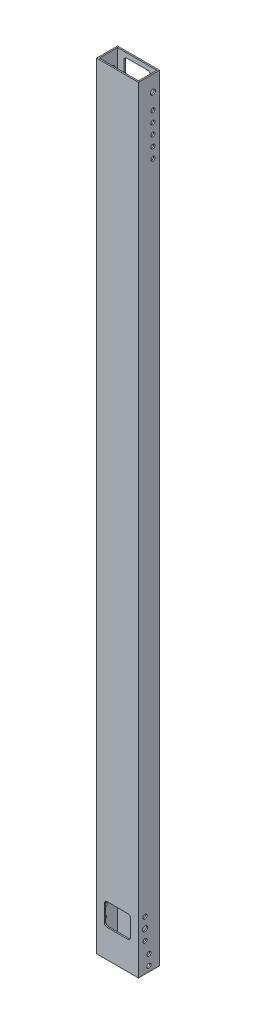
SolidWorks part; units mm, degrees
material "6061-T6 (SS)"
ref_plane "Front Plane" through (0, 0, 0) normal (0, 0, 1) x (1, 0, 0)
ref_plane "Top Plane" through (0, 0, 0) normal (0, 1, 0) x (1, 0, 0)
ref_plane "Right Plane" through (0, 0, 0) normal (1, 0, 0) x (0, 0, -1)
sketch "Sketch1" plane through (0, 0, 0) normal (0, 0, 1) x (1, 0, 0)
  line L1 (-25.4, -469.9) -> (25.4, -469.9)
  line L2 (-25.4, -469.9) -> (-25.4, 469.9)
  line L3 (-25.4, 469.9) -> (25.4, 469.9)
  line L4 (25.4, -469.9) -> (25.4, 469.9)
  line L5 (-25.4, -469.9) -> (25.4, 469.9) construction
  line L6 (-25.4, 469.9) -> (25.4, -469.9) construction
  point P0 (0, 0)
  dimension "D1" = 50.8
  dimension "D2" = 939.8
extrude "Boss-Extrude1" add sketch "Sketch1" along normal mid plane 25.4
shell "Shell1" thickness 1.5875 removed face at (0, -469.9, 0) removed face at (0, 469.9, 0)
sketch "Sketch3" plane through (0, 0, 0) normal (1, 0, 0) x (0, 0, -1)
  line L0 (-12.7, -469.9) -> (12.7, -469.9) construction
  circle A0 centre (0, -463.55) radius 2.4892
  circle A1 centre (0, -450.85) radius 2.4892
  point P6 (0, -469.9)
  dimension "D1" = 4.9784
  dimension "D2" = 6.35
  dimension "D3" = 12.7
extrude "Cut-Extrude1" cut sketch "Sketch3" against normal through all both and the other way through all
sketch "Sketch4" plane through (0, 0, 0) normal (1, 0, 0) x (0, 0, -1)
  line L4 (-12.7, -469.9) -> (12.7, -469.9) construction
  line L5 (-12.7, 469.9) -> (-12.7, -469.9) construction
  circle A3 centre (-4.7625, -422.275) radius 3.175
  circle A4 centre (-4.7625, -409.575) radius 2.4892
  circle A5 centre (-4.7625, -434.975) radius 2.4892
  dimension "D7" = 6.35
  dimension "D8" = 4.9784
  dimension "D9" = 12.7
  dimension "D10" = 12.7
  dimension "D11" = 47.625
  dimension "D12" = 7.9375
extrude "Cut-Extrude2" cut sketch "Sketch4" against normal through all both and the other way through all
sketch "Sketch5" plane through (0, 0, 0) normal (0, 0, 1) x (1, 0, 0)
  line L0 (-25.4, -469.9) -> (25.4, -469.9) construction
  line L1 (-15.875, -408.7812) -> (15.875, -408.7812)
  line L2 (-15.875, -408.7812) -> (-15.875, -435.7687)
  line L3 (-15.875, -435.7687) -> (15.875, -435.7687)
  line L4 (15.875, -408.7812) -> (15.875, -435.7687)
  point P4 (0, -435.7687)
  point P7 (0, -469.9)
  point P8 (15.875, -422.275)
  dimension "D1" = 31.75
  dimension "D2" = 26.9875
  dimension "D3" = 47.625
extrude "Cut-Extrude3" cut sketch "Sketch5" along normal through all
fillet "Fillet1" radius 3.175 4 edges at (-15.875, -435.7687, 11.9062) (15.875, -435.7687, 11.9062) (-15.875, -408.7812, 11.9062) (15.875, -408.7812, 11.9062)
sketch "Sketch6" plane through (0, 0, 0) normal (1, 0, 0) x (0, 0, -1)
  line L0 (12.7, 469.9) -> (12.7, -469.9) construction
  line L1 (-12.7, 469.9) -> (12.7, 469.9) construction
  circle A0 centre (4.7625, 450.85) radius 3.175
  dimension "D1" = 6.35
  dimension "D2" = 7.9375
  dimension "D3" = 19.05
extrude "Cut-Extrude4" cut sketch "Sketch6" against normal through all both and the other way through all
sketch "Sketch7" plane through (0, 0, 0) normal (0, 0, 1) x (1, 0, 0)
  line L0 (25.4, 469.9) -> (-25.4, 469.9) construction
  line L1 (15.875, 464.3438) -> (-15.875, 464.3437)
  line L2 (15.875, 464.3438) -> (15.875, 437.3562)
  line L3 (15.875, 437.3562) -> (-15.875, 437.3562)
  line L4 (-15.875, 464.3437) -> (-15.875, 437.3562)
  point P5 (0, 464.3437)
  point P8 (0, 469.9)
  point P9 (-15.875, 450.85)
  dimension "D1" = 26.9875
  dimension "D2" = 31.75
  dimension "D3" = 19.05
extrude "Cut-Extrude5" cut sketch "Sketch7" against normal through all
fillet "Fillet2" radius 3.175 4 edges at (15.875, 437.3562, -11.9062) (-15.875, 437.3562, -11.9062) (-15.875, 464.3437, -11.9062) (15.875, 464.3438, -11.9062)
sketch "Sketch8" plane through (0, 0, 0) normal (1, 0, 0) x (0, 0, -1)
  line L0 (12.7, 469.9) -> (12.7, -469.9) construction
  line L1 (-12.7, 469.9) -> (12.7, 469.9) construction
  circle A0 centre (4.7625, 431.8) radius 2.4892
  circle A1 centre (4.7625, 419.1) radius 2.4892
  circle A2 centre (4.7625, 406.4) radius 2.4892
  circle A3 centre (4.7625, 393.7) radius 2.4892
  circle A4 centre (4.7625, 381) radius 2.4892
  dimension "D3" = 4.9784
  dimension "D1" = 7.9375
  dimension "D2" = 38.1
  dimension "D5" = 12.7
  dimension "D4" = 5
extrude "Cut-Extrude6" cut sketch "Sketch8" against normal through all both and the other way through all
